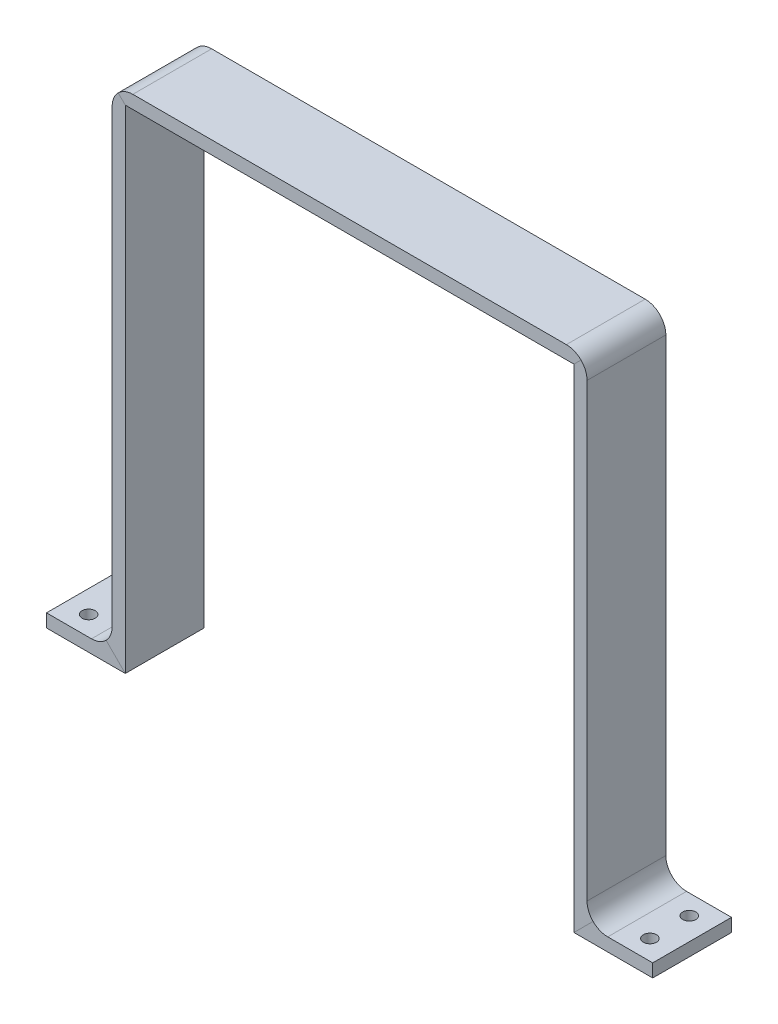
SolidWorks part; units mm, degrees
ref_plane "Front Plane" through (0, 0, 0) normal (0, 0, 1) x (1, 0, 0)
ref_plane "Top Plane" through (0, 0, 0) normal (0, 1, 0) x (1, 0, 0)
ref_plane "Right Plane" through (0, 0, 0) normal (1, 0, 0) x (0, 0, -1)
sketch "Sketch1" plane through (0, 0, 0) normal (0, 0, 1) x (1, 0, 0)
  line L0 (0, 0) -> (38.1, 0)
  line L1 (38.1, 0) -> (38.1, 237.998)
  line L2 (38.1, 237.998) -> (146.558, 237.998)
  dimension "D1" = 108.458
  dimension "D2" = 38.1
  dimension "D3" = 237.998
sketch "Sketch2" plane through (0, 0, 0) normal (1, 0, 0) x (0, 0, -1)
  line L1 (0, 0) -> (38.1, 0)
  line L2 (0, 0) -> (0, 6.35)
  line L3 (0, 6.35) -> (38.1, 6.35)
  line L4 (38.1, 0) -> (38.1, 6.35)
  dimension "D1" = 6.35
  dimension "D2" = 38.1
sweep "Sweep1" add profiles "Sketch2" path "Sketch1"
fillet "Fillet1" radius 10 2 edges at (31.75, 6.35, -19.05) (31.75, 244.348, -19.05)
sketch "Sketch3" plane through (0, 6.35, 0) normal (0, 1, 0) x (1, 0, 0)
  line L0 (10.875, 28.575) -> (10.875, 9.525) construction
  line L2 (0, 0) -> (21.75, 0) construction
  line L3 (0, 38.1) -> (0, 0) construction
  circle A0 centre (10.875, 28.575) radius 3.175
  circle A1 centre (10.875, 9.525) radius 3.175
  point P4 (10.875, 19.05)
  point P5 (10.875, 8.4803)
  point P9 (10.875, 0)
  point P11 (0, 19.05)
  dimension "D2" = 6.35
  dimension "D1" = 19.05
extrude "Cut-Extrude1" cut sketch "Sketch3" against normal up to next
mirror "Mirror1" about plane through (146.558, 237.998, 0) normal (-1, 0, 0) of "Fillet1", "Sweep1", "Cut-Extrude1"
